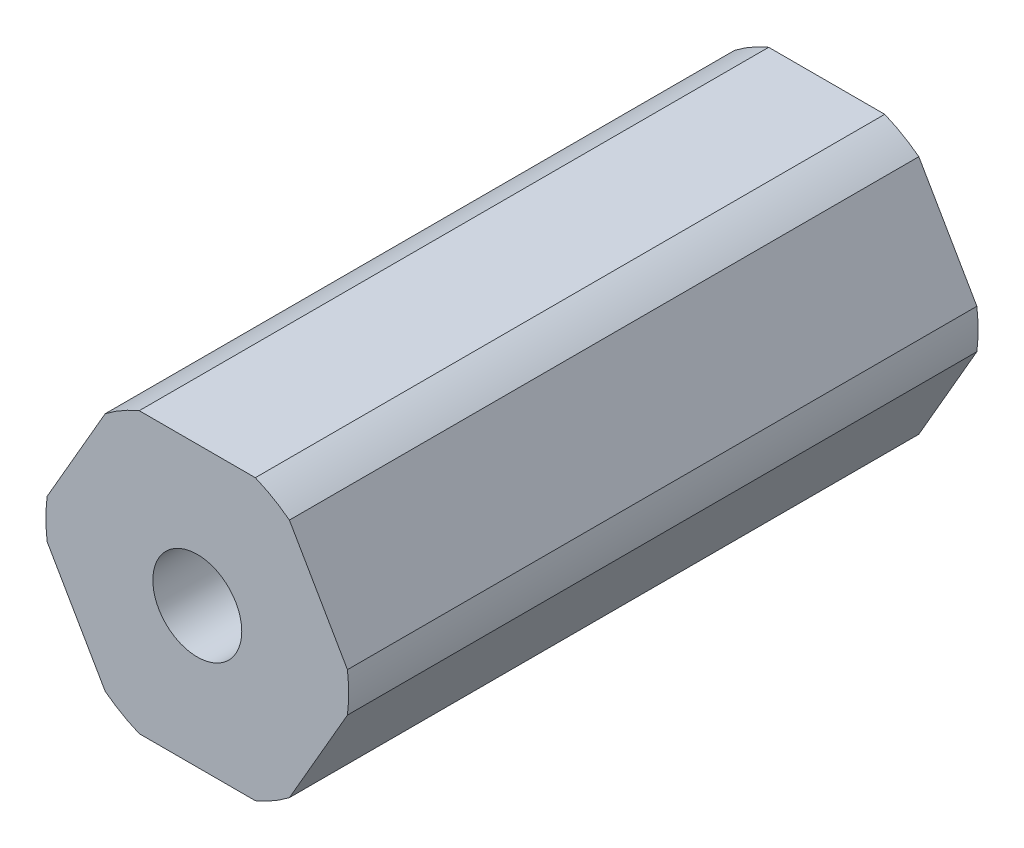
SolidWorks part; units mm, degrees
material "7075-T6 (SN)"
ref_plane "Front Plane" through (0, 0, 0) normal (0, 0, 1) x (1, 0, 0)
ref_plane "Top Plane" through (0, 0, 0) normal (0, 1, 0) x (1, 0, 0)
ref_plane "Right Plane" through (0, 0, 0) normal (1, 0, 0) x (0, 0, -1)
sketch "Sketch1" plane through (0, 0, 0) normal (0, 0, 1) x (1, 0, 0)
  line L1 (7.3323, 0) -> (3.6662, 6.35)
  line L2 (3.6662, 6.35) -> (-3.6662, 6.35)
  line L3 (-3.6662, 6.35) -> (-7.3323, 0)
  line L4 (-7.3323, 0) -> (-3.6662, -6.35)
  line L5 (-3.6662, -6.35) -> (3.6662, -6.35)
  line L6 (3.6662, -6.35) -> (7.3323, 0)
  circle A0 centre (0, 0) radius 6.35 construction
  circle A1 centre (0, 0) radius 2.0193
  circle A2 centre (0, 0) radius 6.875
  dimension "D1" = 12.7
  dimension "D2" = 4.0386
  dimension "D3" = 13.75
extrude "Boss-Extrude1" add sketch "Sketch1" along normal mid plane 28.575 contours L1 A2 L2 L3 L4 L5 L6 A1 region at (6.6736, 0.4353, 0)
hole_wizard "#10-32 Tapped Hole1" positions "3DSketch1" profile "Sketch3" tap size "#10-32" standard "ANSI Inch"
sketch3d "3DSketch1"
  circle A0 centre (0, 0, -14.2875) radius 2.0193 construction
  circle A1 centre (0, 0, 14.2875) radius 2.0193 construction
  point P0 (0, 0, 14.2875)
  point P2 (0, 0, -14.2875)
  point P6 (0, 0, -12.2682)
  point P9 (0, 0, 16.3068)
sketch "Sketch3" plane through (0, 0, 14.2875) normal (1, 0, 0) x (0, -1, 0)
  line L0 (0, 0) -> (0, 13.1513)
  line L1 (0, 13.1513) -> (2.0193, 11.938)
  line L2 (2.0193, 11.938) -> (2.0193, 0)
  line L5 (2.0193, 0) -> (0, 0)
  line L10 (0, 13.1513) -> (-2.0193, 11.938) construction
  line L11 (0, -6.35) -> (0, 107.95) construction
  dimension "Tap Drill Dia." = 4.0386
  dimension "Tap Drill Depth" = 11.938
  dimension "Drill Angle" = 118
cosmetic thread "Hole Thread1" parameters "D1"=9.652, "D2"=4.826
cosmetic thread "Hole Thread2" parameters "D1"=9.652, "D2"=4.826
equation "\"D3@Sketch1\"=13.75mm"
